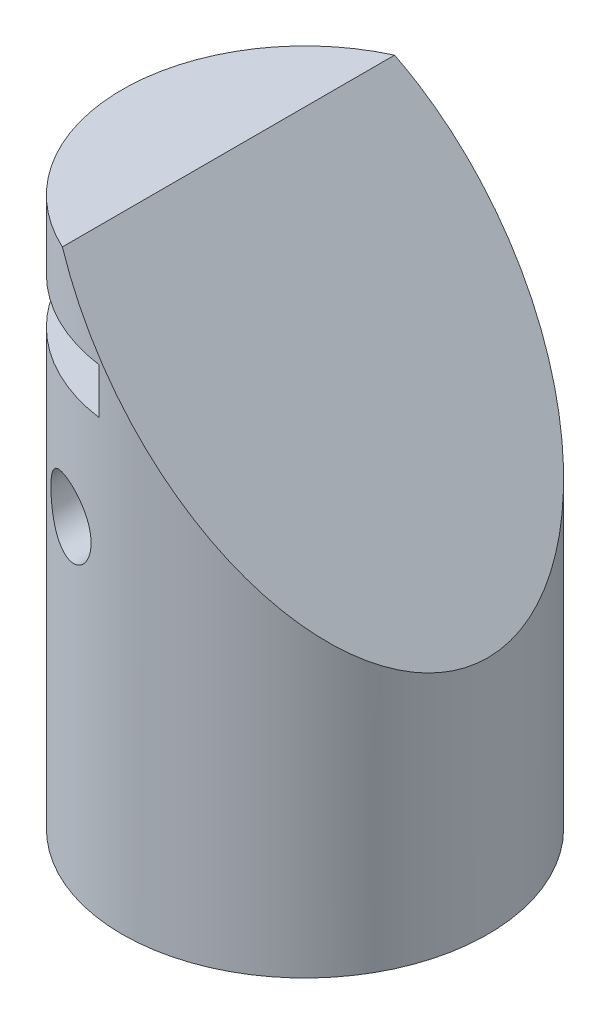
SolidWorks part; units mm, degrees
ref_plane "Front Plane" through (0, 0, 0) normal (0, 0, 1) x (1, 0, 0)
ref_plane "Top Plane" through (0, 0, 0) normal (0, 1, 0) x (1, 0, 0)
ref_plane "Right Plane" through (0, 0, 0) normal (1, 0, 0) x (0, 0, -1)
sketch "Sketch1" plane through (0, 0, 0) normal (0, 1, 0) x (1, 0, 0)
  circle A0 centre (131.5824, -99.1446) radius 40
  circle A1 centre (131.5824, -99.1446) radius 25
  dimension "D1" = 80
  dimension "D2" = 50
extrude "Boss-Extrude1" add sketch "Sketch1" along normal blind 120 from offset 20 contours A0
extrude "Cut-Extrude1" cut sketch "Sketch1<4>" along normal blind 40 from surface contours A1 region at (131.5824, 0, 99.1446) starting at face at (131.5824, 20, 139.1446)
sketch "Sketch1<4>" plane through (0, 0, 0) normal (0, 1, 0) x (1, 0, 0) same geometry as "Sketch1"
sketch "Sketch2" plane through (0, 0, 0) normal (0, 0, 1) x (1, 0, 0)
  line L0 (91.5824, 20) -> (171.5824, 20) construction
  line L1 (91.5824, 140) -> (91.5824, 20) construction
  line L2 (113.1672, 142) -> (173.5824, 70)
  line L3 (173.5824, 70) -> (173.5824, 142)
  line L4 (173.5824, 142) -> (113.1672, 142)
  line L5 (89.5824, 125) -> (126.1265, 125)
  line L6 (126.1265, 125) -> (126.1265, 115)
  line L7 (126.1265, 115) -> (89.5824, 115)
  line L8 (89.5824, 115) -> (89.5824, 125)
  line L9 (171.5824, 140) -> (91.5824, 140) construction
  line L10 (171.5824, 20) -> (171.5824, 140) construction
  circle A0 centre (116.5824, 90) radius 7.5
  dimension "D1" = 15
  dimension "D2" = 70
  dimension "D3" = 25
  dimension "D4" = 1
  dimension "D5" = 2
  dimension "D6" = 2
  dimension "D7" = 50
  dimension "D8" = 40
  dimension "D9" = 10
  dimension "D10" = 15
  dimension "D11" = 2
extrude "Cut-Extrude2" cut sketch "Sketch2" along normal through all
